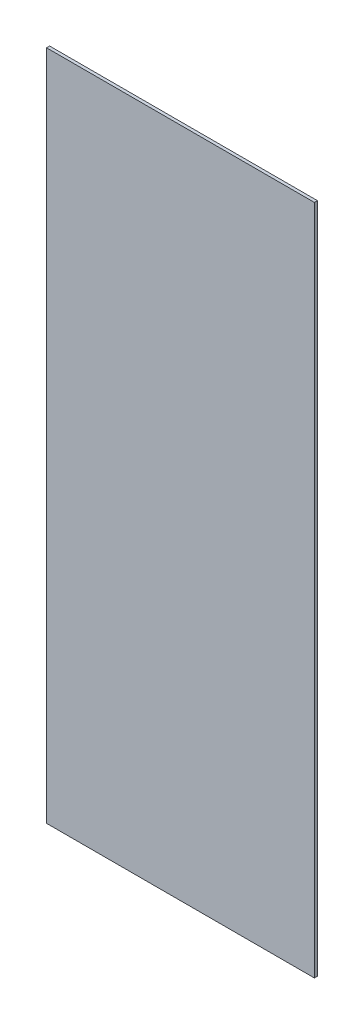
SolidWorks part; units mm, degrees
ref_plane "Спереди" through (0, 0, 0) normal (0, 0, 1) x (1, 0, 0)
ref_plane "Сверху" through (0, 0, 0) normal (0, 1, 0) x (1, 0, 0)
ref_plane "Справа" through (0, 0, 0) normal (1, 0, 0) x (0, 0, -1)
sketch "Эскиз1" plane through (0, 0, 0) normal (0, 0, 1) x (1, 0, 0)
  line L0 (0, -5) -> (0, 425) construction
  line L1 (524, -883) -> (0, -883)
  line L2 (524, -883) -> (524, 431)
  line L3 (524, 431) -> (0, 431)
  line L4 (0, -883) -> (0, 431)
  line L5 (518, 431) -> (0, 431) construction
  line L6 (524, -5) -> (524, 425) construction
  line L8 (518, -877) -> (524, -877) construction
  dimension "D1" = 6
extrude "Бобышка-Вытянуть1" add sketch "Эскиз1" against normal blind 6
equation "\"Толщина стенки\" = 6"
equation "\"Ширина груза\"= 420"
equation "\"Глубина груза\"= 490"
equation "\"Высота груза\"= 297"
equation "\"Ширина ячейки\"= \"Ширина груза\" + 10"
equation "\"Глубина ячейки\"= \"Глубина груза\" + 10"
equation "\"Высота ячейки\"= \"Высота груза\" + 10 + 13"
equation "\"Колво ячеек ширина\"= 2"
equation "\"Колво ячеек высота\"= 2"
equation "\"Крепление дверцы\"= 5 "
equation "\"Ширина рейки\"= \"Толщина шестерни\""
equation "\"Высота рейки\"= 20"
equation "\"Высота пола\"= \"Толщина стенки\" * 2"
equation "\"Колво полозьев\"= 5"
equation "\"Отступ рейки\"= 20"
equation "\"Глубина каретки\"= \"Глубина ячейки\" + 30 + \"Мотор Y высота корпуса\" + 20"
equation "\"Длинна рейки\"= ( \"Ширина ячейки\" + \"Толщина стенки\" + \"Крепление дверцы\" ) * \"Колво ячеек ширина\" + \"Ширина ячейки выгрузки\" * \"Колво выгрузки\" + \"Толщина стенки\""
equation "\"Отступ шпильки\"= 26"
equation "\"Диаметр шпильки\"= 5"
equation "\"Длинна шпильки\"= ( \"Высота ячейки\" + \"Толщина стенки\" + \"Высота пола\" ) * \"Колво ячеек высота\" + ( \"Толщина стенки\" + \"Отступ рейки\" ) * 2 "
equation "\"Ширина пластины\"= 50  "
equation "\"Высота зона выгрузки\"= \"Высота ячейки\" * 2 + \"Толщина стенки\" * 2"
equation "\"Колво выгрузки\"= 1"
equation "\"Ширина ячейки выгрузки\"= \"Ширина ячейки\" + \"Толщина стенки\" + \"Отступ крепления мотора фиксации\"*2"
equation "\"Отступ крепления мотора фиксации\" = 30"
equation "\"Мотор X ширина корпуса\"= 42.3"
equation "\"Мотор X высота корпуса\"= 42.3"
equation "\"Мотор X длина корпуса\"= 40"
equation "\"Мотор X вылет вала\"= 19.8"
equation "\"Мотор Y ширина корпуса\"= 42.3"
equation "\"Мотор Y высота корпуса\"= 42.3"
equation "\"Мотор Y длина корпуса\"= 48"
equation "\"Мотор Y вылет вала\"= 30"
equation "\"Мотор Z ширина корпуса\"= 42"
equation "\"Мотор Z высота корпуса\"= 42"
equation "\"Мотор Z длина корпуса\"= 40"
equation "\"Мотор Z вылет вала\"= 23"
equation "\"Мотор диаметр вала ПРЕДВ\"= 5"
equation "\"Мотор шаг крепления ПРЕДВ\"= 31"
equation "\"Мотор диаметр отверстий ПРЕДВ\"= 3"
equation "\"Мотор глубина отверстий ПРЕДВ\"= 4.5"
equation "\"Мотор диаметр буртика ПРЕДВ\"= 22"
equation "\"Мотор высота буртика ПРЕДВ\"= 2"
equation "\"Мотор диаметр шкива ПРЕДВ\"= 16"
equation "\"Мотор длина шкива ПРЕДВ\"= 12"
equation "\"Мотор отступ шкива ПРЕДВ\"= 5"
equation "\"Мотор X шаг градусов\"= 1.8"
equation "\"Мотор Y шаг градусов\"= 1.8"
equation "\"Мотор Z шаг градусов\"= 1.8"
equation "\"Мотор Y диаметр ротора\"= 25.78"
equation "\"Толщина шестерни\"= 10"
equation "\"D1@Бобышка-Вытянуть1\"=\"Толщина стенки\""
equation "\"D1@Эскиз1\"=\"Толщина стенки\""
